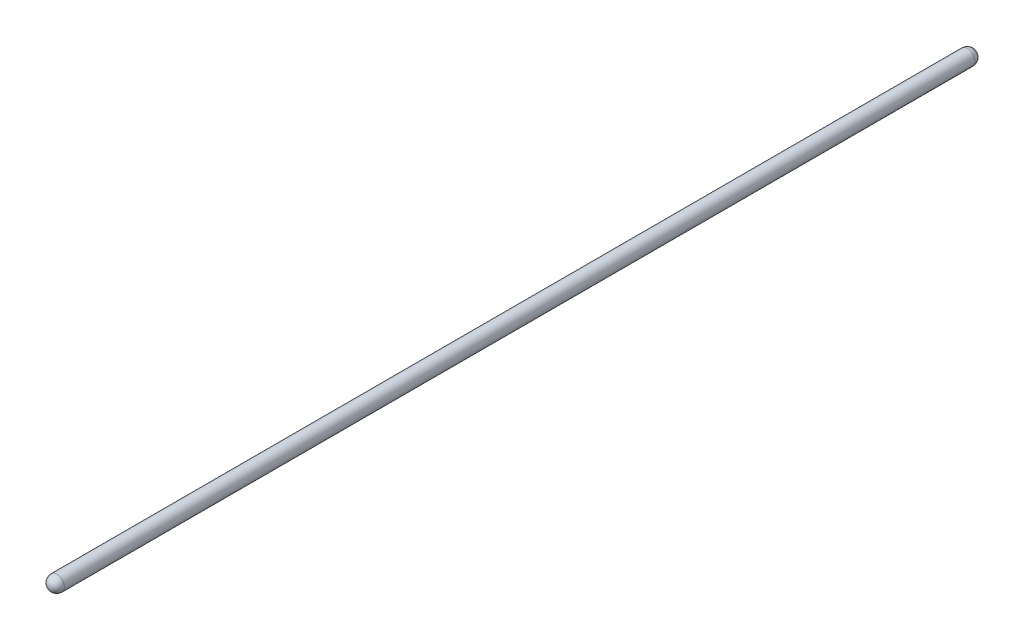
SolidWorks part; units mm, degrees
ref_plane "Plan1" through (0, 0, 0) normal (0, 0, 1) x (1, 0, 0)
ref_plane "Plan2" through (0, 0, 0) normal (0, 1, 0) x (1, 0, 0)
ref_plane "Plan3" through (0, 0, 0) normal (1, 0, 0) x (0, 0, -1)
sketch "Esquisse2" plane through (0, 0, 0) normal (0, 0, 1) x (1, 0, 0)
  circle A0 centre (0, 0) radius 0.5
  dimension "D1" = 1
extrude "Base-Extrusion" add sketch "Esquisse2" along normal blind 60
sketch "Esquisse7" plane through (0, 0, 0) normal (0, 1, 0) x (1, 0, 0)
  line L0 (0, -66.0954) -> (0, -50) construction
  line L1 (0, -60) -> (0, 0) construction
  line L2 (0, -60) -> (0, -60.5)
  line L3 (-0.5, -60) -> (0, -60)
  arc A0 (-0.5, -60) -> (0, -60.5) centre (0, -60) ccw
  dimension "D1" = 1
revolve "Boss.-Révol.1" add sketch "Esquisse7" angle 360 about L0
sketch "Esquisse8" plane through (0, 0, 0) normal (0, 1, 0) x (1, 0, 0)
  line L0 (0, 0) -> (-0.5, 0)
  line L1 (0, 7.9938) -> (0, -10) construction
  line L2 (0, -60) -> (0, 0) construction
  line L3 (0, 0) -> (0, 0.5)
  arc A0 (0, 0.5) -> (-0.5, 0) centre (0, 0) ccw
  dimension "D1" = 1
revolve "Boss.-Révol.2" add sketch "Esquisse8" angle 360 about L1
ref_axis "Axe1" through (0, 0, 62.1717) along (0, 0, -1)
ref_plane "Plan5" through (0, 0, -0.5) normal (0, 0, 1) x (1, 0, 0)
ref_plane "Plan6" through (0, 0, 60.5) normal (0, 0, 1) x (1, 0, 0)
ref_point "Point1"
